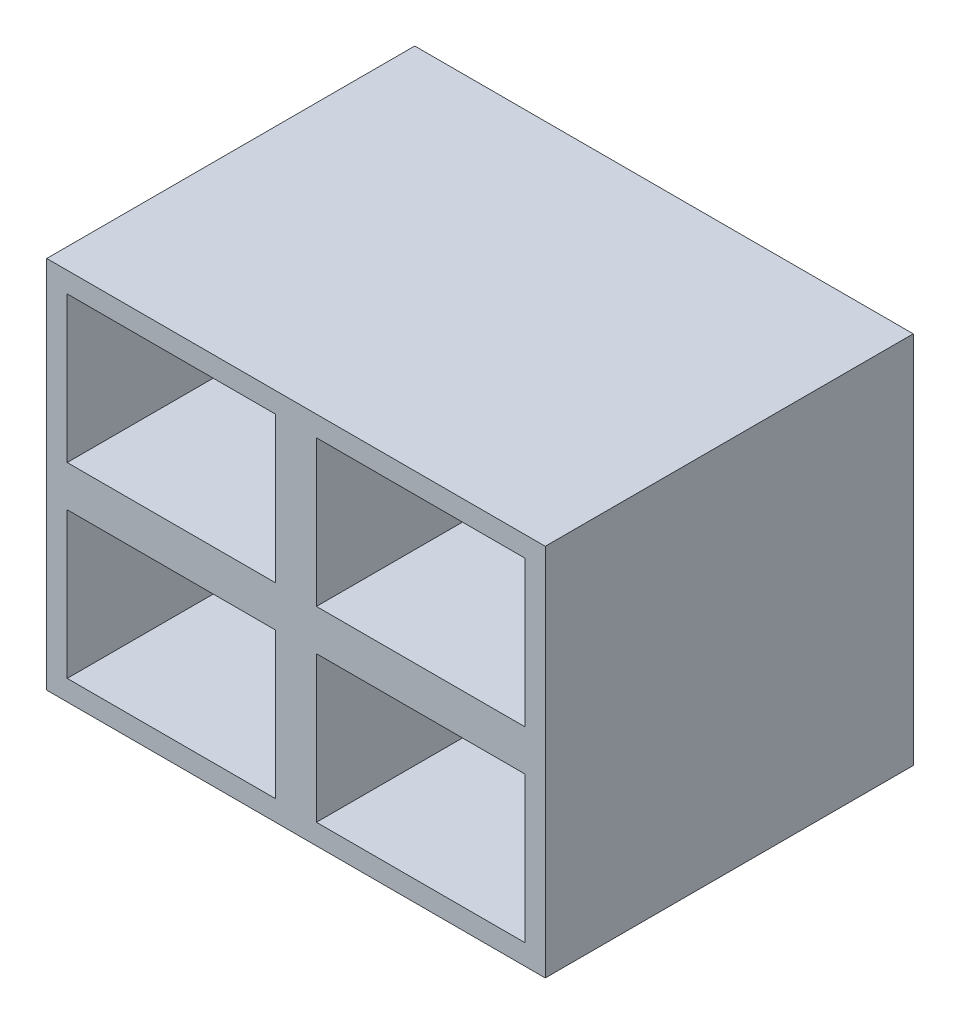
SolidWorks part; units mm, degrees
ref_plane "Front" through (0, 0, 0) normal (0, 0, 1) x (1, 0, 0)
ref_plane "Top" through (0, 0, 0) normal (0, 1, 0) x (1, 0, 0)
ref_plane "Right" through (0, 0, 0) normal (1, 0, 0) x (0, 0, -1)
sketch "Sketch1" plane through (0, 0, 0) normal (0, 0, 1) x (1, 0, 0)
  line L1 (609.6, 457.2) -> (-609.6, 457.2)
  line L2 (609.6, 457.2) -> (609.6, -457.2)
  line L3 (609.6, -457.2) -> (-609.6, -457.2)
  line L4 (-609.6, 457.2) -> (-609.6, -457.2)
  line L5 (609.6, 457.2) -> (-609.6, -457.2) construction
  line L6 (609.6, -457.2) -> (-609.6, 457.2) construction
  point P0 (0, 0)
  dimension "D1" = 1219.2
  dimension "D2" = 914.4
extrude "Boss-Extrude1" add sketch "Sketch1" along normal blind 900
sketch "Sketch2" plane through (0, 0, 900) normal (0, 0, 1) x (1, 0, 0)
  line L0 (0, -457.2) -> (0, 457.2) construction
  line L1 (609.6, 457.2) -> (-609.6, 457.2) construction
  line L2 (609.6, 0) -> (-609.6, 0) construction
  line L3 (-609.6, 457.2) -> (-609.6, -457.2) construction
  line L4 (559.6, 407.2) -> (50, 407.2)
  line L5 (-50, 407.2) -> (-559.6, 407.2)
  line L6 (-50, 407.2) -> (-50, 50)
  line L7 (-50, 50) -> (-559.6, 50)
  line L8 (-559.6, 407.2) -> (-559.6, 50)
  line L9 (-50, 407.2) -> (-559.6, 50) construction
  line L10 (-50, 50) -> (-559.6, 407.2) construction
  line L11 (50, 407.2) -> (50, 50)
  line L12 (559.6, 407.2) -> (559.6, 50)
  line L13 (559.6, 50) -> (50, 50)
  line L14 (559.6, -50) -> (50, -50)
  line L15 (50, -50) -> (50, -407.2)
  line L16 (559.6, -50) -> (559.6, -407.2)
  line L17 (559.6, -407.2) -> (50, -407.2)
  line L18 (-50, -50) -> (-559.6, -50)
  line L19 (-559.6, -50) -> (-559.6, -407.2)
  line L20 (-50, -50) -> (-50, -407.2)
  line L21 (-50, -407.2) -> (-559.6, -407.2)
  point P0 (-304.8, 228.6)
  point P6 (0, 0)
  point P12 (0, 0)
  dimension "D1" = 50
  dimension "D2" = 50
  dimension "D3" = 50
  dimension "D4" = 50
  dimension "D7" = 50
  dimension "D8" = 50
  dimension "D5" = 2
  dimension "D6" = 2
extrude "Cut-Extrude1" cut sketch "Sketch2" against normal blind 900
equation "\"inside\"= 9895.75 * 2"
equation "\"outside\"= 9945.85 * 2"
equation "\"cut\"=1219.2"
equation "\"centeringline\"=584.6"
equation "\"framewidth\"=50"
